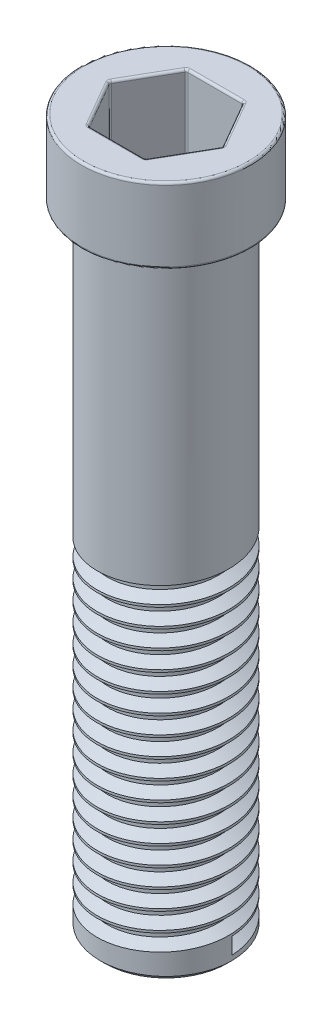
SolidWorks part; units mm, degrees
material "AISI 4140 Steel, quenched & tempered"
ref_plane "Front Plane" through (0, 0, 0) normal (1, 0, 0) x (0, 1, 0)
ref_plane "Top Plane" through (0, 0, 0) normal (0, 0, 1) x (0, 1, 0)
ref_plane "Right Plane" through (0, 0, 0) normal (0, 1, 0) x (-1, 0, 0)
sketch "Sketch1" plane through (0, 0, 0) normal (1, 0, 0) x (0, 1, 0)
  line L0 (-122.9929, 0) -> (42.9358, 0) construction
  line L1 (0, 23.268) -> (0, -20.4189) construction
  line L2 (8, 0) -> (8, 9)
  line L3 (8, 9) -> (0, 9)
  line L4 (0, 9) -> (0, 7)
  line L5 (0, 7) -> (-67, 7)
  line L6 (-67, 7) -> (-67, 0)
  line L7 (-67, 0) -> (8, 0)
  dimension "D1" = 8
  dimension "D2" = 18
  dimension "D3" = 14
  dimension "D4" = 67
revolve "Revolve1" add sketch "Sketch1" angle 360 about L0
sketch "Sketch2" plane through (0, 8, 0) normal (0, 1, 0) x (-1, 0, 0)
  line L1 (3, -5.1962) -> (6, 0)
  line L2 (6, 0) -> (3, 5.1962)
  line L3 (3, 5.1962) -> (-3, 5.1962)
  line L4 (-3, 5.1962) -> (-6, 0)
  line L5 (-6, 0) -> (-3, -5.1962)
  line L6 (-3, -5.1962) -> (3, -5.1962)
  circle A0 centre (0, 0) radius 5.1962 construction
  dimension "D1" = 6
extrude "Cut-Extrude1" cut sketch "Sketch2" against normal blind 8
ref_axis "Axis1" through (0, 16, 0) along (0, -1, 0)
thread "Thread2" pitch 2 method cut profile "Thread Profile2" start angle 0, offset 1, length 35, pitch 2, diameter 14
ref_plane "Plane2" through (7, -66, 0) normal (0, 0, 1) x (1, 0, 0)
sketch "Thread Profile2" plane through (7, -66, 0) normal (0, 0, 1) x (1, 0, 0)
  line L0 (0, 0) -> (0, 2) construction
  line L11 (0, 0) -> (0, 1.75)
  line L12 (0, 1.75) -> (-1.0825, 1.125)
  line L13 (-1.0825, 1.125) -> (-1.0825, 0.625)
  line L15 (-1.0825, 0.625) -> (0, 0)
  line L17 (-1.0825, 0.875) -> (0, 0.875) construction
  point P2 (0, 0)
  dimension "Pitch" = 2
  dimension "Profile_Angle" = 60
  dimension "Profile_Land" = 0.5
  dimension "Profile_Height" = 1.0825
chamfer "Chamfer1" distance 0.5 angle 45 1 edges at (0, -67, -7)
fillet "Fillet1" radius 0.25 20 edges at (0, 0, -9) (0, 8, -9) (0, 8, -5.1962) (-4.5, 8, -2.5981) (-4.5, 8, 2.5981) (0, 8, 5.1962) (4.5, 8, 2.5981) (4.5, 8, -2.5981) (0, 0, -5.1962) (-4.5, 0, -2.5981) (-4.5, 0, 2.5981) (0, 0, 5.1962) (4.5, 0, 2.5981) (4.5, 0, -2.5981) (-3, 4, -5.1962) (-3, 4, 5.1962) (3, 4, 5.1962) (6, 4, 0) (3, 4, -5.1962) (-6, 4, 0)
